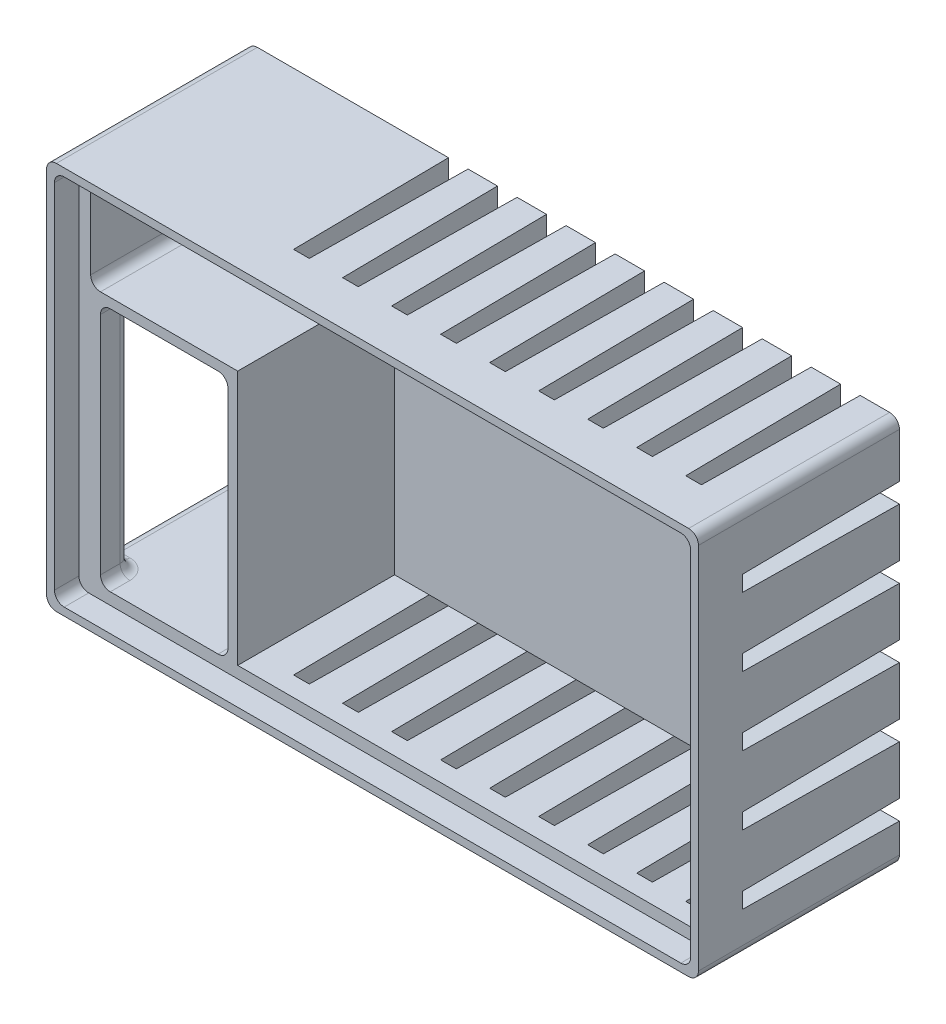
SolidWorks part; units mm, degrees
ref_plane "Front Plane" through (0, 0, 0) normal (0, 0, 1) x (1, 0, 0)
ref_plane "Top Plane" through (0, 0, 0) normal (0, 1, 0) x (1, 0, 0)
ref_plane "Right Plane" through (0, 0, 0) normal (1, 0, 0) x (0, 0, -1)
sketch "Sketch1" plane through (0, 0, 0) normal (0, 0, 1) x (1, 0, 0)
  line L1 (0, 0) -> (66.5, 0)
  line L2 (0, 0) -> (0, 39.6)
  line L3 (0, 39.6) -> (66.5, 39.6)
  line L4 (66.5, 0) -> (66.5, 39.6)
  dimension "D1" = 39.6
  dimension "D2" = 66.5
extrude "Boss-Extrude1" add sketch "Sketch1" along normal blind 2
sketch "Sketch2" plane through (0, 0, 2) normal (0, 0, 1) x (1, 0, 0)
  line L0 (66.5, 0) -> (66.5, 39.6) construction
  line L1 (0, 0) -> (66.5, 0) construction
  line L2 (0, 39.6) -> (0, 0) construction
  line L3 (66.5, 39.6) -> (0, 39.6) construction
  line L4 (66.5, 0) -> (66.5, 39.6)
  line L5 (0, 0) -> (66.5, 0)
  line L6 (0, 39.6) -> (0, 0)
  line L7 (66.5, 39.6) -> (0, 39.6)
  line L8 (64.5, 37.6) -> (2, 37.6)
  line L9 (2, 37.6) -> (2, 2)
  line L10 (2, 2) -> (64.5, 2)
  line L11 (64.5, 2) -> (64.5, 37.6)
  dimension "D1" = 2
extrude "Boss-Extrude2" add sketch "Sketch2" along normal blind 16
sketch "Sketch3" plane through (0, 0, 18) normal (0, 0, 1) x (1, 0, 0)
  line L0 (66.5, 0) -> (66.5, 39.6) construction
  line L1 (0, 0) -> (66.5, 0) construction
  line L2 (0, 39.6) -> (0, 0) construction
  line L3 (66.5, 39.6) -> (0, 39.6) construction
  line L4 (66.5, 0) -> (66.5, 39.6)
  line L5 (0, 0) -> (66.5, 0)
  line L6 (0, 39.6) -> (0, 0)
  line L7 (66.5, 39.6) -> (0, 39.6)
  line L8 (65.7, 38.8) -> (0.8, 38.8)
  line L9 (0.8, 38.8) -> (0.8, 0.8)
  line L10 (0.8, 0.8) -> (65.7, 0.8)
  line L11 (65.7, 0.8) -> (65.7, 38.8)
  dimension "D1" = 0.8
extrude "Boss-Extrude3" add sketch "Sketch3" along normal blind 2.5
sketch "Sketch5" plane through (0, 0, 0) normal (0, 0, -1) x (-1, 0, 0)
  line L0 (0, 39.6) -> (0, 0) construction
  line L1 (0, 2) -> (-16, 2)
  line L2 (0, 2) -> (0, 27)
  line L3 (0, 27) -> (-16, 27)
  line L4 (-16, 2) -> (-16, 27)
  line L5 (0, 0) -> (-66.5, 0) construction
  dimension "D1" = 2
  dimension "D2" = 25
  dimension "D3" = 16
extrude "Cut-Extrude2" cut sketch "Sketch5" against normal blind 15
sketch "Sketch6" plane through (0, 0, 2) normal (0, 0, 1) x (1, 0, 0)
  line L0 (2, 27) -> (16, 27) construction
  line L1 (16, 27) -> (16, 2) construction
  line L2 (2, 27) -> (16, 27)
  line L3 (16, 27) -> (16, 2)
  line L4 (2, 27) -> (2, 28)
  line L5 (2, 37.6) -> (2, 2) construction
  line L6 (2, 28) -> (17, 28)
  line L7 (17, 28) -> (17, 2)
  line L8 (2, 2) -> (64.5, 2) construction
  line L9 (17, 2) -> (16, 2)
  dimension "D1" = 1
  dimension "D2" = 1
extrude "Boss-Extrude4" add sketch "Sketch6" along normal up to surface (16 mm away) up to face at (33.25, 19.8, 18)
fillet "Fillet1" radius 1 12 edges at (66.5, 39.6, 10.25) (66.5, 0, 10.25) (0, 0, 10.25) (0, 39.6, 10.25) (0.8, 0.8, 19.25) (2, 28, 10) (0.8, 38.8, 19.25) (2, 37.6, 10) (64.5, 37.6, 10) (65.7, 38.8, 19.25) (64.5, 2, 10) (65.7, 0.8, 19.25)
sketch "Sketch7" plane through (0, 39.6, 0) normal (0, 1, 0) x (1, 0, 0)
  line L0 (62.5, 0) -> (62.3, -16)
  line L1 (65.5, 0) -> (1, 0) construction
  line L2 (62.3, -16) -> (60.7, -16)
  line L3 (60.7, -16) -> (60.5, 0)
  line L4 (60.5, 0) -> (62.5, 0)
  line L5 (61.5, 0) -> (61.5, -16) construction
  line L6 (66.5, 0) -> (66.5, -20.5) construction
  dimension "D1" = 16
  dimension "D2" = 2
  dimension "D3" = 1.6
  dimension "D4" = 5
extrude "Cut-Extrude3" cut sketch "Sketch7" against normal blind 2
pattern_linear "LPattern1" count 9 spacing 5 along (-1, 0, 0) of "Cut-Extrude3"
ref_plane "Plane1" through (0, 19.8, 0) normal (0, 1, 0) x (1, 0, 0)
mirror "Mirror1" about plane through (0, 19.8, 0) normal (0, 1, 0) of "LPattern1", "Cut-Extrude3"
sketch "Sketch8" plane through (66.5, 0, 0) normal (1, 0, 0) x (0, 0, -1)
  line L0 (0, 6) -> (0, 4)
  line L1 (0, 4) -> (-16, 4.2)
  line L2 (-16, 4.2) -> (-16, 5.8)
  line L3 (-16, 5.8) -> (0, 6)
  line L4 (0, 5) -> (-16, 5) construction
  line L5 (0, 1) -> (0, 38.6) construction
  line L6 (0, 0) -> (-20.5, 0) construction
  dimension "D1" = 2
  dimension "D2" = 1.6
  dimension "D3" = 16
  dimension "D4" = 5
extrude "Cut-Extrude4" cut sketch "Sketch8" against normal blind 2
pattern_linear "LPattern2" count 5 spacing 7 along (0, 1, 0) of "Cut-Extrude4"
sketch "Sketch9" plane through (0, 0, 15) normal (0, 0, -1) x (-1, 0, 0)
  line L0 (0, 27) -> (-16, 27) construction
  line L1 (-2, 2) -> (-3, 2)
  line L2 (-2, 2) -> (-2, 27)
  line L3 (-2, 27) -> (-3, 27)
  line L4 (-3, 2) -> (-3, 27)
  dimension "D1" = 1
extrude "Boss-Extrude5" add sketch "Sketch9" against normal up to surface (3 mm away) up to face at (9, 14.5, 18)
fillet "Fillet2" radius 1 10 edges at (3, 2, 16.5) (3, 14.5, 15) (0, 14.5, 15) (1.5, 2, 15) (0, 27, 7.5) (1.5, 27, 15) (3, 27, 16.5) (16, 2, 9) (16, 27, 9) (0, 2, 7.5)
sketch "Sketch10" plane through (0, 0, 0) normal (0, 0, -1) x (-1, 0, 0)
  line L0 (-1, 0) -> (-20.5, 0) construction
  line L1 (-17, 3) -> (-29, 3)
  line L2 (-17, 3) -> (-17, 27)
  line L3 (-17, 27) -> (-29, 27)
  line L4 (-29, 3) -> (-29, 27)
  line L5 (-3, 3) -> (-3, 26) construction
  line L6 (-1, 27) -> (-15, 27) construction
  dimension "D2" = 14
  dimension "D3" = 12
  dimension "D4" = 3
extrude "Cut-Extrude5" cut sketch "Sketch10" against normal blind 0.4
fillet "Fillet3" radius 2 4 edges at (17, 27, 0.2) (29, 27, 0.2) (29, 3, 0.2) (17, 3, 0.2)
equation "\"D2@Sketch6\"=\"D1@Sketch6\""
